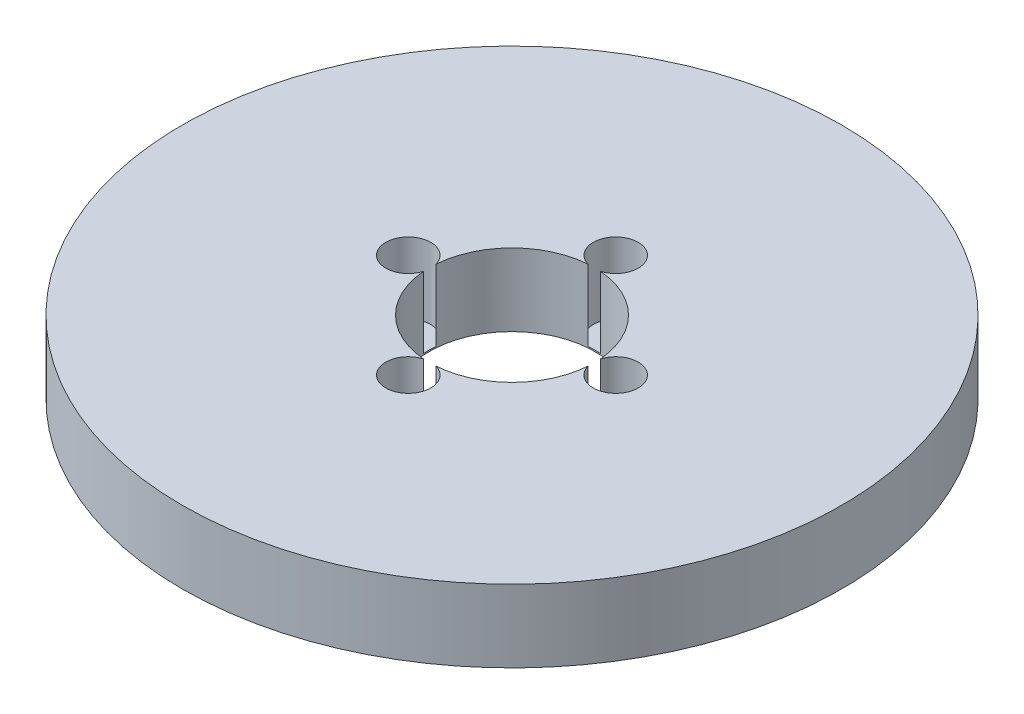
SolidWorks part; units mm, degrees
ref_plane "Front Plane" through (0, 0, 0) normal (0, 0, 1) x (1, 0, 0)
ref_plane "Top Plane" through (0, 0, 0) normal (0, 1, 0) x (1, 0, 0)
ref_plane "Right Plane" through (0, 0, 0) normal (1, 0, 0) x (0, 0, -1)
sketch "Sketch1" plane through (0, 0, 0) normal (0, 1, 0) x (1, 0, 0)
  circle A0 centre (0, 0) radius 50
  dimension "FLANGE_OD" = 100
extrude "Boss-Extrude1" add sketch "Sketch1" along normal blind 11
sketch "Sketch2" plane through (0, 0, 0) normal (0, 1, 0) x (1, 0, 0)
  circle A0 centre (0, 0) radius 12.5
  dimension "BORE_D" = 25
extrude "Cut-Extrude1" cut sketch "Sketch2" along normal through all
sketch "Sketch3" plane through (0, 11, 0) normal (0, 1, 0) x (1, 0, 0)
  circle A0 centre (0, 0) radius 15.7399 construction
  circle A1 centre (-15.7399, 0) radius 3.409
  dimension "BOLT_D" = 6.818
  dimension "BOLT_PCD" = 31.4797
extrude "Cut-Extrude2" cut sketch "Sketch3" against normal blind 10.8036
pattern_circular "CirPattern1" count 4 over 360 about axis through (0, 0, 0) along (0, 1, 0) of "Cut-Extrude2"
